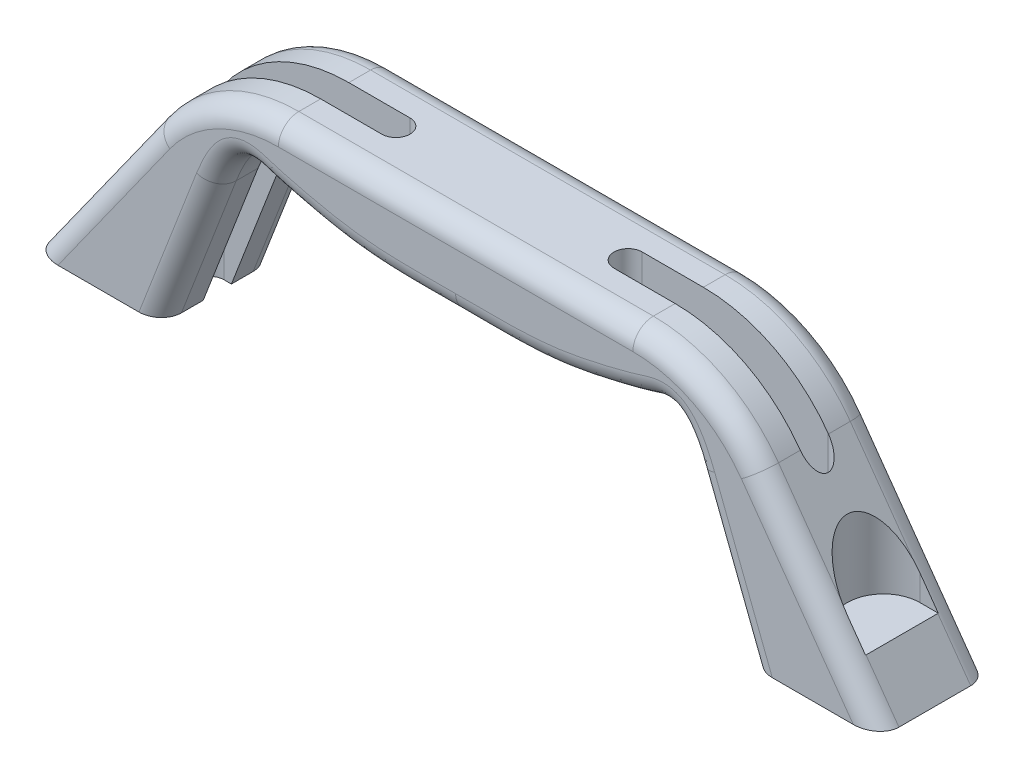
SolidWorks part; units mm, degrees
ref_plane "Plan de face" through (0, 0, 0) normal (0, 0, 1) x (1, 0, 0)
ref_plane "Plan de dessus" through (0, 0, 0) normal (0, 1, 0) x (1, 0, 0)
ref_plane "Plan de droite" through (0, 0, 0) normal (1, 0, 0) x (0, 0, -1)
sketch "Esquisse1" plane through (0, 0, 0) normal (0, 0, 1) x (1, 0, 0)
  line L0 (0, 0) -> (0, 30) construction
  line L1 (46.8093, 27.6774) -> (57.5, 0)
  line L2 (-82.5, 0) -> (-59.0022, 32.9267)
  line L3 (-34.5827, 45.5) -> (34.5827, 45.5)
  line L5 (-46.8093, 27.6774) -> (-57.5, 0)
  line L6 (-57.5, 0) -> (-82.5, 0)
  line L7 (82.5, 0) -> (59.0022, 32.9267)
  line L8 (57.5, 0) -> (82.5, 0)
  line L9 (0, 45.5) -> (0, 67.7608) construction
  arc A0 (-59.0022, 32.9267) -> (-34.5827, 45.5) centre (-34.5827, 15.5) cw
  arc A1 (59.0022, 32.9267) -> (34.5827, 45.5) centre (34.5827, 15.5) ccw
  spline S0 degree 3 poles (0, 30) (-7.8472, 30) (-17.2504, 29.7466) (-29.6721, 32.386) (-39.3923, 34.9503) (-43.2799, 36.8148) (-46.8093, 27.6774) knots 0 0 0 0 0.411285 0.644431 0.761425 1 1 1 1
  spline S1 degree 3 poles (0, 30) (7.8472, 30) (17.2504, 29.7466) (29.6721, 32.386) (39.3923, 34.9503) (43.2799, 36.8148) (46.8093, 27.6774) knots 0 0 0 0 0.411285 0.644431 0.761425 1 1 1 1
  dimension "D4" = 30
  dimension "D1" = 45.5
  dimension "D2" = 165
  dimension "D3" = 25
  dimension "D5" = 15.5
extrude "Boss.-Extru.1" add sketch "Esquisse1" along normal blind 11 and the other way blind 11
sketch "Esquisse2" plane through (0, 45.5, 0) normal (0, 1, 0) x (1, 0, 0)
  line L0 (-58.95, 0) -> (-22.65, 0) construction
  line L1 (-58.95, 2.75) -> (-22.65, 2.75)
  line L2 (-58.95, -2.75) -> (-22.65, -2.75)
  line L3 (0, 0) -> (0, 51.2487) construction
  line L4 (58.95, 0) -> (22.65, 0) construction
  line L5 (58.95, 2.75) -> (22.65, 2.75)
  line L6 (58.95, -2.75) -> (22.65, -2.75)
  arc A0 (-58.95, 2.75) -> (-58.95, -2.75) centre (-58.95, 0) ccw
  arc A1 (-22.65, -2.75) -> (-22.65, 2.75) centre (-22.65, 0) ccw
  arc A2 (58.95, 2.75) -> (58.95, -2.75) centre (58.95, 0) cw
  arc A3 (22.65, -2.75) -> (22.65, 2.75) centre (22.65, 0) cw
  point P3 (-40.8, 0)
  point P10 (40.8, 0)
  dimension "D1" = 2.75
  dimension "D2" = 36.3
  dimension "D3" = 45.3
extrude "Enlèv. mat.-Extru.2" cut sketch "Esquisse2" against normal up to surface (45.5 mm away) up to face at (-70, 0, 0)
fillet "Congé1" radius 4 18 edges at (-52.1546, 13.8387, -11) (52.1546, 13.8387, -11) (70.7511, 16.4634, -11) (48.3159, 42.1721, -11) (-70.7511, 16.4634, -11) (-48.3159, 42.1721, -11) (-52.1546, 13.8387, 11) (52.1546, 13.8387, 11) (70.7511, 16.4634, 11) (48.3159, 42.1721, 11) (-70.7511, 16.4634, 11) (-48.3159, 42.1721, 11) (0, 45.5, -11) (0, 45.5, 11)
sketch "Esquisse3" plane through (0, 45.5, 0) normal (0, 1, 0) x (1, 0, 0)
  line L0 (-82.5, 7) -> (-82.5, -7) construction
  line L1 (-72.5, 7.1) -> (-82.5, 7.1)
  line L2 (-82.5, 7.1) -> (-82.5, -7.1)
  line L3 (-82.5, -7.1) -> (-72.5, -7.1)
  line L4 (0, 0) -> (0, 33.7284) construction
  line L5 (82.5, -7.1) -> (72.5, -7.1)
  line L6 (82.5, 7.1) -> (82.5, -7.1)
  line L7 (72.5, 7.1) -> (82.5, 7.1)
  arc A0 (-72.5, -7.1) -> (-72.5, 7.1) centre (-72.5, 0) ccw
  arc A1 (72.5, -7.1) -> (72.5, 7.1) centre (72.5, 0) cw
  dimension "D1" = 14.2
  dimension "D2" = 10
extrude "Enlèv. mat.-Extru.3" cut sketch "Esquisse3" against normal blind 36.5
